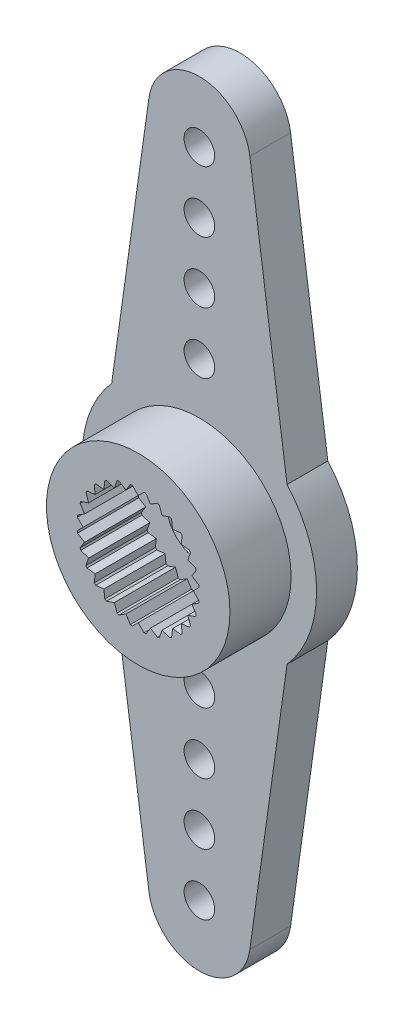
SolidWorks part; units mm, degrees
ref_plane "Plan de face" through (0, 0, 0) normal (0, 0, 1) x (1, 0, 0)
ref_plane "Plan de dessus" through (0, 0, 0) normal (0, 1, 0) x (1, 0, 0)
ref_plane "Plan de droite" through (0, 0, 0) normal (1, 0, 0) x (0, 0, -1)
sketch "Esquisse1" plane through (0, 0, 0) normal (0, 0, 1) x (1, 0, 0)
  circle A0 centre (0, 0) radius 5.75
  circle A1 centre (0, 0) radius 1.6
  dimension "D1" = 11.5
  dimension "D2" = 3.2
extrude "Boss.-Extru.1" add sketch "Esquisse1" along normal blind 5
sketch "Esquisse2" plane through (0, 0, 5) normal (0, 0, 1) x (1, 0, 0)
  circle A0 centre (0, 0) radius 3
  dimension "D1" = 6
extrude "Enlèv. mat.-Extru.1" cut sketch "Esquisse2" against normal blind 3
sketch "Esquisse3" plane through (0, 0, 5) normal (0, 0, 1) x (1, 0, 0)
  circle A0 centre (0, 0) radius 5.75
  circle A1 centre (0, 0) radius 4.5
  circle A2 centre (0, 0) radius 3 construction
  circle A3 centre (0, 0) radius 5.75 construction
  dimension "D1" = 1.5
extrude "Enlèv. mat.-Extru.2" cut sketch "Esquisse3" against normal blind 3
sketch "Esquisse4" plane through (0, 0, 0) normal (0, 0, -1) x (-1, 0, 0)
  line L0 (-4.3, 3.8174) -> (-2.4759, 16.8466)
  line L1 (2.4759, 16.8466) -> (4.3, 3.8174)
  line L2 (-5.2729, 19) -> (6.8365, 19) construction
  line L3 (0, 0) -> (0, 24.2526) construction
  circle A0 centre (0, 0) radius 5.75 construction
  arc A1 (-2.4759, 16.8466) -> (2.4759, 16.8466) centre (0, 16.5) cw
  arc A2 (-4.3, 3.8174) -> (4.3, 3.8174) centre (0, 0) cw
  dimension "D2" = 2.5
  dimension "D1" = 8.6
  dimension "D3" = 19
extrude "Boss.-Extru.2" add sketch "Esquisse4" against normal up to surface (2 mm away) up to face at (4.5, 0, 2)
pattern_circular "Répétition circulaire1" count 2 every 180 about axis through (0, 0, 5) along (0, 0, -1) of "Boss.-Extru.2"
sketch "Esquisse5" plane through (0, 0, 0) normal (0, 0, -1) x (-1, 0, 0)
  line L0 (0, 0) -> (0, 20.4605) construction
  circle A0 centre (0, 7) radius 0.75
  circle A1 centre (0, 10) radius 0.75
  circle A2 centre (0, 13) radius 0.75
  circle A3 centre (0, 16) radius 0.75
  dimension "D5" = 1.5
  dimension "D6" = 1.5
  dimension "D7" = 1.5
  dimension "D8" = 1.5
  dimension "D1" = 7
  dimension "D2" = 3
  dimension "D3" = 3
  dimension "D4" = 3
extrude "Enlèv. mat.-Extru.3" cut sketch "Esquisse5" against normal blind 3
pattern_circular "Répétition circulaire2" count 2 every 180 about axis through (0, 0, 5) along (0, 0, -1) of "Enlèv. mat.-Extru.3"
sketch "Esquisse6" plane through (0, 0, 5) normal (0, 0, 1) x (1, 0, 0)
  line L0 (-1.598, 3) -> (1.8482, 3) construction
  line L1 (0, 0) -> (0, 5.9454) construction
  line L2 (-0.3, 3) -> (0, 2.7)
  line L3 (0, 2.7) -> (0.3, 3)
  line L4 (0.3, 3) -> (-0.3, 3)
  circle A0 centre (0, 0) radius 3 construction
  dimension "D1" = 0.3
  dimension "D2" = 0.6
extrude "Boss.-Extru.3" add sketch "Esquisse6" against normal up to surface (3 mm away) up to face at (1.6, 0, 2)
pattern_circular "Répétition circulaire3" count 28 over 360 about axis through (0, 0, 2) along (0, 0, 1) of "Boss.-Extru.3"
sketch "Esquisse7" plane through (0, 0, 0) normal (0, 0, -1) x (-1, 0, 0)
  circle A0 centre (0, 0) radius 1.6
  circle A1 centre (0, 0) radius 3
  circle A2 centre (0, 0) radius 1.6 construction
  dimension "D1" = 6
extrude "Enlèv. mat.-Extru.4" cut sketch "Esquisse7" against normal blind 1
sketch "Esquisse8" plane through (0, 0, 0) normal (0, 0, -1) x (-1, 0, 0)
  circle A0 centre (0, 0) radius 3.4
  circle A1 centre (0, 0) radius 4.7
  circle A2 centre (0, 0) radius 3 construction
  dimension "D1" = 0.4
  dimension "D2" = 1.3
extrude "Enlèv. mat.-Extru.5" cut sketch "Esquisse8" against normal blind 1
